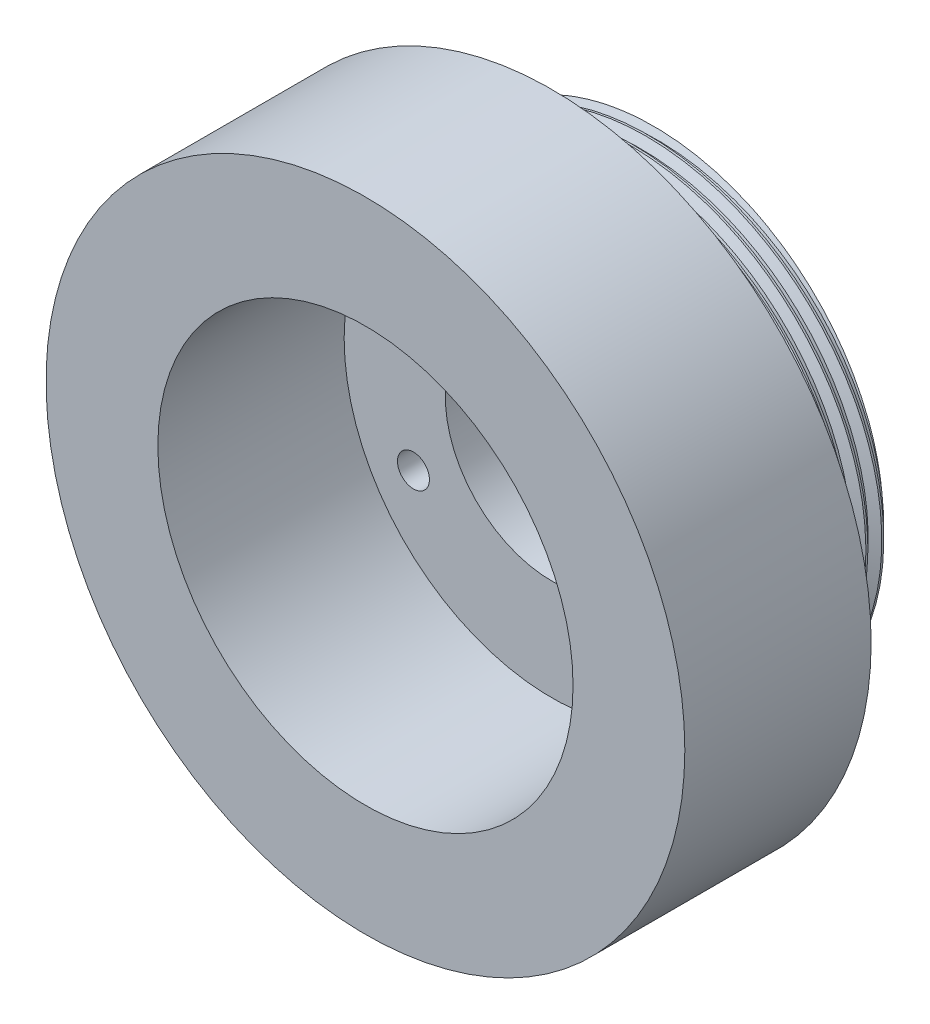
SolidWorks part; units mm, degrees
ref_plane "Front Plane" through (0, 0, 0) normal (0, 0, 1) x (1, 0, 0)
ref_plane "Top Plane" through (0, 0, 0) normal (0, 1, 0) x (1, 0, 0)
ref_plane "Right Plane" through (0, 0, 0) normal (1, 0, 0) x (0, 0, -1)
sketch "Sketch1" plane through (0, 0, 0) normal (0, 0, 1) x (1, 0, 0)
  circle A0 centre (0, 0) radius 10
  circle A2 centre (0, 0) radius 22
  dimension "D1" = 20
  dimension "D2" = 44
extrude "Boss-Extrude1" add sketch "Sketch1" against normal blind 10 contours A2 A0 region at (-21.3777, 0, 0)
sketch "Sketch3" plane through (0, 0, 0) normal (0, 0, 1) x (1, 0, 0)
  circle A0 centre (0, 0) radius 19.5
  circle A1 centre (0, 0) radius 30
  dimension "D1" = 39
  dimension "D2" = 60
extrude "Boss-Extrude3" add sketch "Sketch3" along normal blind 17.5 contours A1 | A0 region at (-29.1515, 0, 0)
sketch "Sketch5" plane through (0, 0, 0) normal (0, 0, 1) x (1, 0, 0)
  circle A0 centre (0, 15) radius 1.5
  circle A1 centre (12.9904, -7.5) radius 1.5
  circle A2 centre (-12.9904, -7.5) radius 1.5
  point P10 (0, 0)
  dimension "D1" = 3
  dimension "D2" = 15
  dimension "D3" = 3
extrude "Cut-Extrude1" cut sketch "Sketch5" against normal through all
thread "Thread1" pitch 1.5 method cut profile "Thread Profile2" start angle 0, offset 2, length 0, pitch 1.5, diameter 44
ref_plane "Plane2" through (22, 0, -12) normal (0, -1, 0) x (1, 0, 0)
sketch "Thread Profile2" plane through (22, 0, -12) normal (0, -1, 0) x (1, 0, 0)
  line L0 (0, 0) -> (0, 1.5) construction
  line L11 (0, 0) -> (0, 1.3125)
  line L12 (0, 1.3125) -> (-0.8119, 0.8437)
  line L13 (-0.8119, 0.8437) -> (-0.8119, 0.4687)
  line L15 (-0.8119, 0.4687) -> (0, 0)
  line L17 (-0.8119, 0.6562) -> (0, 0.6562) construction
  point P2 (0, 0)
  dimension "Pitch" = 1.5
  dimension "Profile_Angle" = 60
  dimension "Profile_Land" = 0.375
  dimension "Profile_Height" = 0.8119
